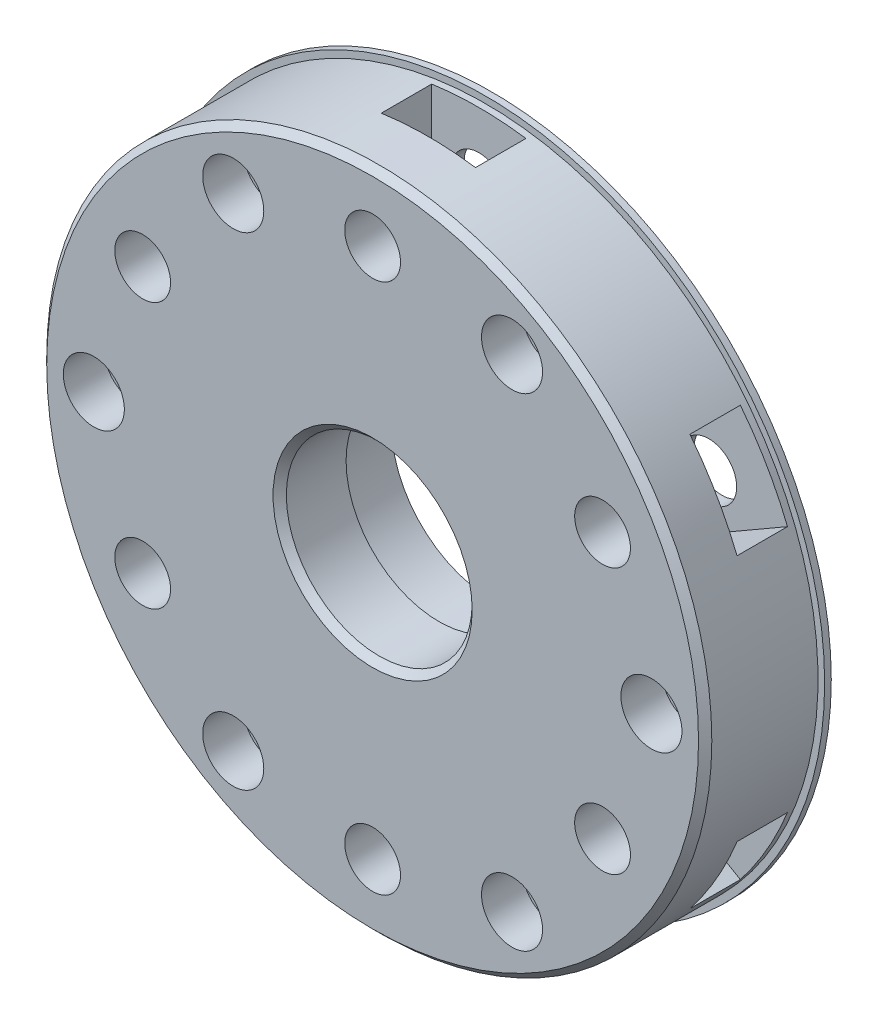
SolidWorks part; units mm, degrees
material "ABS"
ref_plane "Front Plane" through (0, 0, 0) normal (0, 0, 1) x (1, 0, 0)
ref_plane "Top Plane" through (0, 0, 0) normal (0, 1, 0) x (1, 0, 0)
ref_plane "Right Plane" through (0, 0, 0) normal (1, 0, 0) x (0, 0, -1)
sketch "Output Master Sketch" plane through (0, 0, 0) normal (0, 0, 1) x (1, 0, 0)
  circle A0 centre (0, 0) radius 21 construction
  circle A1 centre (21, 0) radius 2.95 construction
  circle A2 centre (10.5, -18.1865) radius 2.95 construction
  circle A3 centre (-10.5, -18.1865) radius 2.95 construction
  circle A4 centre (-21, 0) radius 2.95 construction
  circle A5 centre (-10.5, 18.1865) radius 2.95 construction
  circle A6 centre (10.5, 18.1865) radius 2.95 construction
  circle A7 centre (0, 0) radius 25.05
  point P17 (0, 0)
extrude "Boss-Extrude1" add sketch "Output Master Sketch" along normal blind 9
sketch "Sketch4" plane through (0, 0, 0) normal (0, 0, 1) x (1, 0, 0)
  circle A0 centre (21, 0) radius 2.95
  circle A1 centre (21, 0) radius 2.95 construction
  circle A2 centre (10.5, -18.1865) radius 2.95
  circle A3 centre (-10.5, -18.1865) radius 2.95
  circle A4 centre (-21, 0) radius 2.95
  circle A5 centre (-10.5, 18.1865) radius 2.95
  circle A6 centre (10.5, 18.1865) radius 2.95
  point P17 (0, 0)
  dimension "D1" = 6
extrude "Cut-Extrude1" cut sketch "Sketch4" along normal blind 4
sketch "Sketch5" plane through (0, 0, 0) normal (0, 0, -1) x (-1, 0, 0)
  circle A0 centre (0, 0) radius 25.05
  circle A1 centre (0, 0) radius 25.55
  circle A2 centre (0, 0) radius 25.05 construction
  dimension "D1" = 0.5
extrude "Boss-Extrude2" add sketch "Sketch5" against normal blind 0.5
sketch "Sketch6" plane through (0, 0, 0) normal (0, 0, -1) x (-1, 0, 0)
  circle A0 centre (-21, 0) radius 1.55
  circle A1 centre (-10.5, 18.1865) radius 1.55
  circle A2 centre (10.5, 18.1865) radius 1.55
  circle A3 centre (21, 0) radius 1.55
  circle A4 centre (10.5, -18.1865) radius 1.55
  circle A5 centre (-10.5, -18.1865) radius 1.55
  point P15 (0, 0)
  dimension "D1" = 3.1
  dimension "D2" = 6
extrude "Cut-Extrude2" cut sketch "Sketch6" against normal through all
sketch "Sketch7" plane through (0, 0, 9) normal (0, 0, 1) x (1, 0, 0)
  circle A0 centre (-21, 0) radius 2.3
  circle A1 centre (-10.5, 18.1865) radius 2.3
  circle A2 centre (10.5, 18.1865) radius 2.3
  circle A3 centre (21, 0) radius 2.3
  circle A4 centre (10.5, -18.1865) radius 2.3
  circle A5 centre (-10.5, -18.1865) radius 2.3
  point P16 (0, 0)
  dimension "D1" = 4.6
  dimension "D2" = 6
extrude "Cut-Extrude3" cut sketch "Sketch7" against normal blind 3.1
chamfer "Chamfer1" distance 0.5 angle 45 1 edges at (25.05, 0, 9)
sketch "Sketch8" plane through (0, 0, 0) normal (0, 0, -1) x (-1, 0, 0)
  circle A0 centre (0, 0) radius 7
  dimension "D1" = 14
extrude "Cut-Extrude4" cut sketch "Sketch8" against normal blind 10
sketch "Sketch9" plane through (0, 0, 0) normal (0, 0, -1) x (-1, 0, 0)
  circle A0 centre (0, 0) radius 7.575
  dimension "D1" = 15.15
extrude "Cut-Extrude5" cut sketch "Sketch9" against normal blind 4
sketch "Sketch10" plane through (0, 0, 9) normal (0, 0, 1) x (1, 0, 0)
  line L1 (0, 20) -> (-17.3205, 10) construction
  line L2 (-17.3205, 10) -> (-17.3205, -10) construction
  line L3 (-17.3205, -10) -> (0, -20) construction
  line L4 (0, -20) -> (17.3205, -10) construction
  line L5 (17.3205, -10) -> (17.3205, 10) construction
  line L6 (17.3205, 10) -> (0, 20) construction
  circle A0 centre (0, 0) radius 20 construction
  circle A1 centre (0, 20) radius 2.1
  circle A2 centre (17.3205, 10) radius 2.1
  circle A3 centre (17.3205, -10) radius 2.1
  circle A4 centre (0, -20) radius 2.1
  circle A5 centre (-17.3205, -10) radius 2.1
  circle A6 centre (-17.3205, 10) radius 2.1
  point P22 (0, 0)
  dimension "D1" = 40
  dimension "D2" = 4.2
  dimension "D3" = 6
extrude "M4 Thru" cut sketch "Sketch10" against normal through all
chamfer "Chamfer3" distance 0.5 angle 45 1 edges at (7, 0, 9)
sketch "Sketch11" plane through (0, 0, 9) normal (0, 0, 1) x (1, 0, 0)
  line L1 (0, 24.0992) -> (-3.55, 22.0496)
  line L2 (-3.55, 22.0496) -> (-3.55, 17.9504)
  line L3 (-3.55, 17.9504) -> (0, 15.9008)
  line L4 (0, 15.9008) -> (3.55, 17.9504)
  line L5 (3.55, 17.9504) -> (3.55, 22.0496)
  line L6 (3.55, 22.0496) -> (0, 24.0992)
  circle A0 centre (0, 20) radius 3.55 construction
  dimension "D1" = 7.1
extrude "M4 Hexnut Cut" cut sketch "Sketch11" along normal blind 3.8 from offset 8 offset against normal yes
ref_plane "Plane2" through (0, 22.0496, 0) normal (0, 1, 0) x (1, 0, 0)
sketch "Sketch12" plane through (0, 22.0496, 0) normal (0, 1, 0) x (1, 0, 0)
  line L1 (-3.55, -1) -> (3.55, -1)
  line L2 (-3.55, -1) -> (-3.55, -4.8)
  line L3 (-3.55, -4.8) -> (3.55, -4.8)
  line L4 (3.55, -1) -> (3.55, -4.8)
extrude "M4 Hexnut Slot" cut sketch "Sketch12" along normal through all contours L2 L1 L4 L3
pattern_circular "M4 Hexnut Pattern" count 6 over 360 about axis through (0, 0, 10) along (0, 0, -1) of "M4 Hexnut Cut", "M4 Hexnut Slot" reverse direction yes
